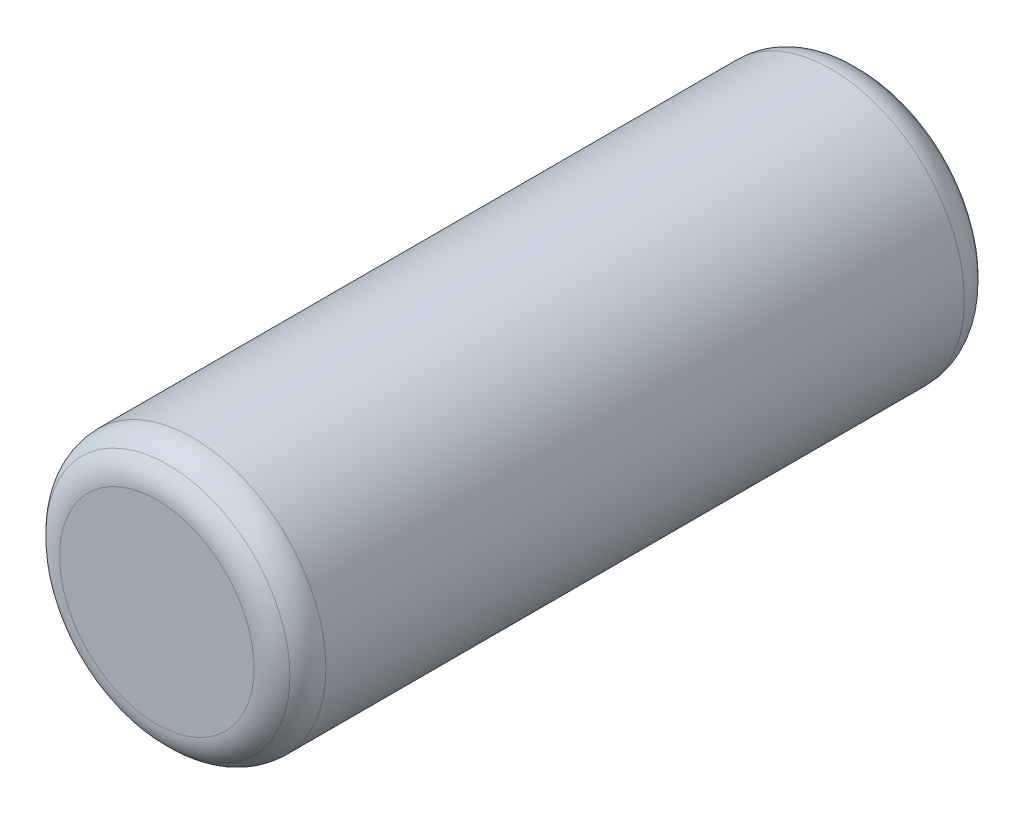
SolidWorks part; units mm, degrees
ref_plane "Front Plane" through (0, 0, 0) normal (0, 0, 1) x (1, 0, 0)
ref_plane "Top Plane" through (0, 0, 0) normal (0, 1, 0) x (1, 0, 0)
ref_plane "Right Plane" through (0, 0, 0) normal (1, 0, 0) x (0, 0, -1)
sketch "Sketch2" plane through (0, 0, 0) normal (0, 0, 1) x (1, 0, 0)
  circle A0 centre (0, 0) radius 3
  dimension "D1" = 6
extrude "Boss-Extrude1" add sketch "Sketch2" against normal blind 15.5 contours A0
sketch "Sketch5" plane through (0, 0, 0) normal (0, 0, 1) x (1, 0, 0)
  circle A0 centre (0, 0) radius 2.75
  dimension "D1" = 5.5
extrude "Boss-Extrude2" add sketch "Sketch5" along normal blind 0.25
fillet "Fillet3" radius 0.75 2 edges at (3, 0, 0) (2.75, 0, 0.25)
sketch "Sketch6" plane through (0, 0, -15.5) normal (0, 0, -1) x (-1, 0, 0)
  circle A0 centre (0, 0) radius 2.75
  dimension "D1" = 5.5
extrude "Boss-Extrude3" add sketch "Sketch6" along normal blind 0.25 contours A0
fillet "Fillet4" radius 0.75 2 edges at (-2.75, 0, -15.75) (3, 0, -15.5)
